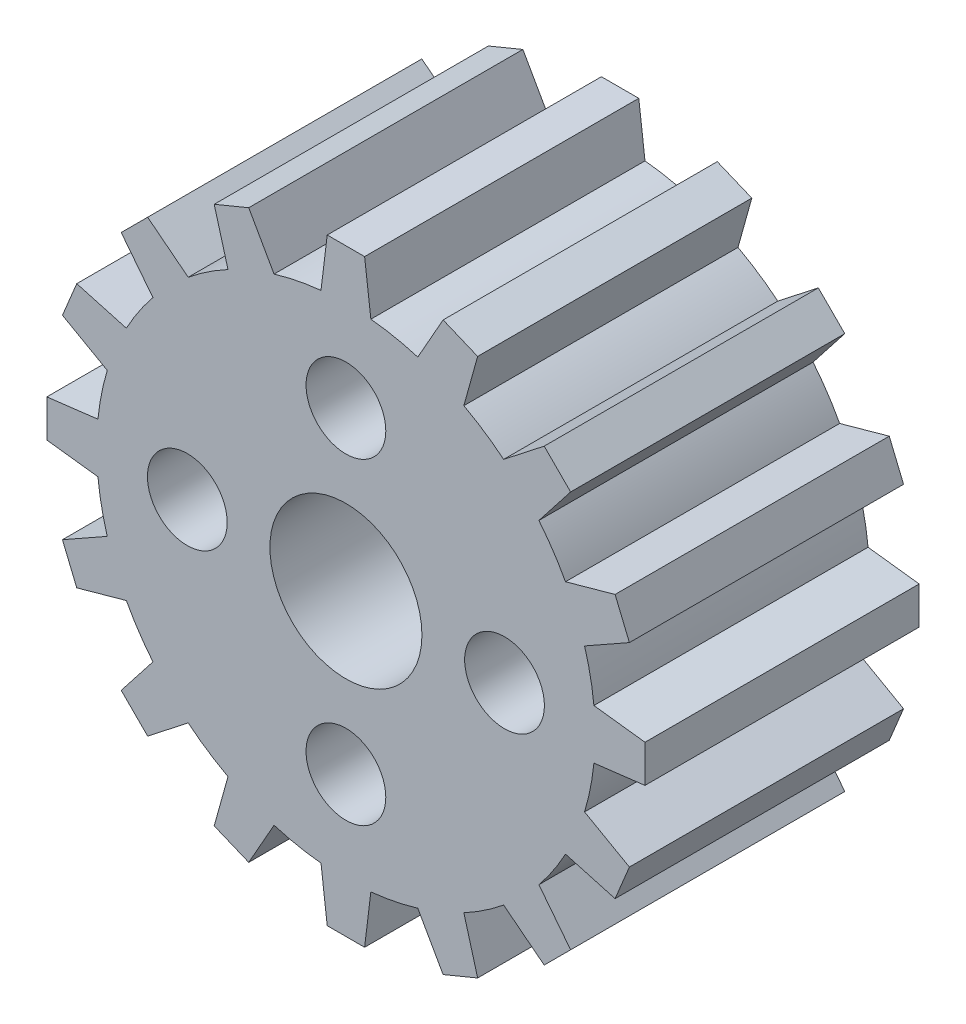
SolidWorks part; units mm, degrees
ref_plane "正面" through (0, 0, 0) normal (0, 0, 1) x (1, 0, 0)
ref_plane "平面" through (0, 0, 0) normal (0, 1, 0) x (1, 0, 0)
ref_plane "右側面" through (0, 0, 0) normal (1, 0, 0) x (0, 0, -1)
sketch "ｽｹｯﾁ1" plane through (0, 0, 0) normal (0, 0, 1) x (1, 0, 0)
  line L0 (-0.75, 12) -> (-1, 9.9499)
  line L1 (-0.75, 12) -> (0.75, 12)
  line L2 (-0.75, 12) -> (-0.75, 8)
  line L3 (-0.75, 8) -> (0.75, 8)
  line L4 (0.75, 12) -> (0.75, 8)
  line L5 (-0.75, 12) -> (0.75, 8) construction
  line L6 (-0.75, 8) -> (0.75, 12) construction
  line L7 (0.75, 12) -> (1, 9.9499)
  line L8 (1, 9.9499) -> (-1, 9.9499)
  line L9 (3.8993, 11.3736) -> (2.8838, 9.5752)
  line L10 (3.8993, 11.3736) -> (5.2851, 10.7995)
  line L11 (5.2851, 10.7995) -> (4.7315, 8.8098)
  line L12 (7.955, 9.0156) -> (6.3285, 7.7427)
  line L13 (7.955, 9.0156) -> (9.0156, 7.955)
  line L14 (9.0156, 7.955) -> (7.7427, 6.3285)
  line L15 (10.7995, 5.2851) -> (8.8098, 4.7315)
  line L16 (10.7995, 5.2851) -> (11.3736, 3.8993)
  line L17 (11.3736, 3.8993) -> (9.5752, 2.8838)
  line L18 (12, 0.75) -> (9.9499, 1)
  line L19 (12, 0.75) -> (12, -0.75)
  line L20 (12, -0.75) -> (9.9499, -1)
  line L21 (11.3736, -3.8993) -> (9.5752, -2.8838)
  line L22 (11.3736, -3.8993) -> (10.7995, -5.2851)
  line L23 (10.7995, -5.2851) -> (8.8098, -4.7315)
  line L24 (9.0156, -7.955) -> (7.7427, -6.3285)
  line L25 (9.0156, -7.955) -> (7.955, -9.0156)
  line L26 (7.955, -9.0156) -> (6.3285, -7.7427)
  line L27 (5.2851, -10.7995) -> (4.7315, -8.8098)
  line L28 (5.2851, -10.7995) -> (3.8993, -11.3736)
  line L29 (3.8993, -11.3736) -> (2.8838, -9.5752)
  line L30 (0.75, -12) -> (1, -9.9499)
  line L31 (0.75, -12) -> (-0.75, -12)
  line L32 (-0.75, -12) -> (-1, -9.9499)
  line L33 (-3.8993, -11.3736) -> (-2.8838, -9.5752)
  line L34 (-3.8993, -11.3736) -> (-5.2851, -10.7995)
  line L35 (-5.2851, -10.7995) -> (-4.7315, -8.8098)
  line L36 (-7.955, -9.0156) -> (-6.3285, -7.7427)
  line L37 (-7.955, -9.0156) -> (-9.0156, -7.955)
  line L38 (-9.0156, -7.955) -> (-7.7427, -6.3285)
  line L39 (-10.7995, -5.2851) -> (-8.8098, -4.7315)
  line L40 (-10.7995, -5.2851) -> (-11.3736, -3.8993)
  line L41 (-11.3736, -3.8993) -> (-9.5752, -2.8838)
  line L42 (-12, -0.75) -> (-9.9499, -1)
  line L43 (-12, -0.75) -> (-12, 0.75)
  line L44 (-12, 0.75) -> (-9.9499, 1)
  line L45 (-11.3736, 3.8993) -> (-9.5752, 2.8838)
  line L46 (-11.3736, 3.8993) -> (-10.7995, 5.2851)
  line L47 (-10.7995, 5.2851) -> (-8.8098, 4.7315)
  line L48 (-9.0156, 7.955) -> (-7.7427, 6.3285)
  line L49 (-9.0156, 7.955) -> (-7.955, 9.0156)
  line L50 (-7.955, 9.0156) -> (-6.3285, 7.7427)
  line L51 (-5.2851, 10.7995) -> (-4.7315, 8.8098)
  line L52 (-5.2851, 10.7995) -> (-3.8993, 11.3736)
  line L53 (-3.8993, 11.3736) -> (-2.8838, 9.5752)
  line L54 (0, 0) -> (1, 9.9499) construction
  line L56 (-6.364, 0) -> (0, -6.364) construction
  line L57 (0, -6.364) -> (6.364, 0) construction
  line L58 (6.364, 0) -> (0, 6.364) construction
  line L59 (0, 6.364) -> (-6.364, 0) construction
  circle A0 centre (0, 0) radius 10
  circle A1 centre (0, 0) radius 3.05
  circle A2 centre (0, 0) radius 4.5 construction
  circle A3 centre (-6.364, 0) radius 1.6
  circle A4 centre (0, 6.364) radius 1.6
  circle A5 centre (6.364, 0) radius 1.6
  circle A6 centre (0, -6.364) radius 1.6
  point P3 (0, 10)
  dimension "D1" = 20
  dimension "D8" = 6.1
  dimension "D10" = 3.2
  dimension "D11" = 3.2
  dimension "D12" = 3.2
  dimension "D13" = 3.2
  dimension "D2" = 1.5
  dimension "D3" = 2
  dimension "D4" = 0
  dimension "D5" = 2
  dimension "D7" = 10
  dimension "D9" = 9
  dimension "D6" = 16
extrude "ﾎﾞｽ - 押し出し1" add sketch "ｽｹｯﾁ1" along normal blind 11 contours A0 L53 L52 L51 | A0 L2 L0 | A0 L4 L1 L2 | A0 L7 L4 | A0 L50 L49 L48 | A0 L47 L46 L45 | A0 L44 L43 L42 | A0 L41 L40 L39 | A0 L38 L37 L36 | A0 L35 L34 L33 | A0 L32 L31 L30 | A0 L29 L28 L27 | A0 L26 L25 L24 | A0 L23 L22 L21 | A0 L20 L19 L18 | A0 L17 L16 L15 | A0 L14 L13 L12 | A0 L11 L10 L9 | A0 L8 L4 L3 L2 A1 | L4 L8 L2 L3 | L4 A0 L2 L8 | L2 A0 L8 | L8 A0 L4 region at (-0.8333, 10.6409, 0) region at (0, 10.9953, 0) region at (-0.8352, 9.9574, 0) region at (-0.875, 9.6674, 0) region at (0.8333, 10.6409, 0) region at (0, 9.9711, 0) region at (0, 8.9749, 0) region at (-4.1882, 10.1112, 0) region at (0.8352, 9.9574, 0) region at (4.1882, 10.1112, 0) region at (-7.7388, 7.7388, 0) region at (7.7388, 7.7388, 0) region at (-10.1112, 4.1882, 0) region at (10.1112, 4.1882, 0) region at (-10.9443, 0, 0) region at (10.9443, 0, 0) region at (-10.1112, -4.1882, 0) region at (-7.7388, -7.7388, 0) region at (10.1112, -4.1882, 0) region at (-4.1882, -10.1112, 0) region at (7.7388, -7.7388, 0) region at (0, -10.9443, 0) region at (4.1882, -10.1112, 0)
ref_axis "軸1" through (0, 0, 11) along (0, 0, -1)
ref_plane "平面1" through (0, 0, 0) normal (0.8315, -0.5556, 0) x (0, 0, -1)
sketch "ｽｹｯﾁ2" plane through (0, 0, 0) normal (0.8315, -0.5556, 0) x (0, 0, -1)
  circle A0 centre (-5.5, 0) radius 1.65
  dimension "D1" = 5.5
  dimension "D2" = 3.3
extrude "ｶｯﾄ - 押し出し3" cut sketch "ｽｹｯﾁ2" against normal through all
